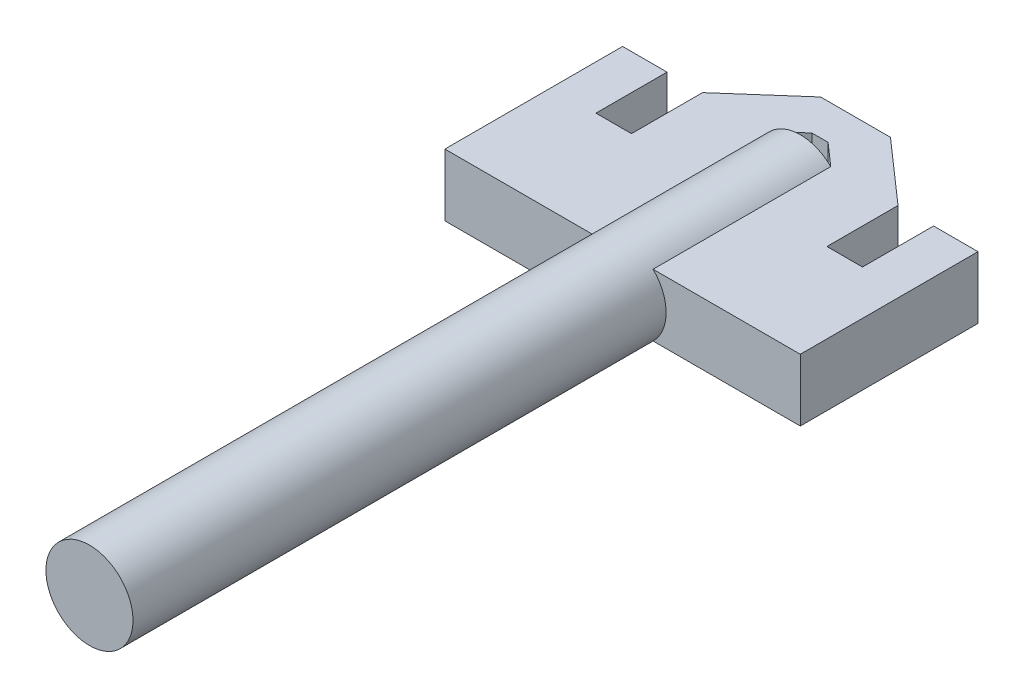
SolidWorks part; units mm, degrees
ref_plane "Front Plane" through (0, 0, 0) normal (0, 0, 1) x (1, 0, 0)
ref_plane "Top Plane" through (0, 0, 0) normal (0, 1, 0) x (1, 0, 0)
ref_plane "Right Plane" through (0, 0, 0) normal (1, 0, 0) x (0, 0, -1)
sketch "Sketch2" plane through (0, 0, 0) normal (0, 0, 1) x (1, 0, 0)
  circle A0 centre (0, 0) radius 2.45
  dimension "D1" = 4.9
extrude "Boss-Extrude1" add sketch "Sketch2" along normal blind 40
sketch "Sketch3" plane through (0, 0, 0) normal (0, 0, -1) x (-1, 0, 0)
  line L0 (-10, 1.75) -> (10, 1.75)
  line L1 (10, 1.75) -> (10, -1.75)
  line L4 (-10, 1.75) -> (-10, -1.75)
  line L5 (-10, -1.75) -> (10, -1.75)
  circle A1 centre (0, 0) radius 2.45 construction
  point P3 (10, 0)
  point P5 (0, 1.75)
  dimension "D1" = 1.75
  dimension "D4" = 20
extrude "Boss-Extrude2" add sketch "Sketch3" against normal blind 10
sketch "Sketch4" plane through (0, 0, 0) normal (0, 0, -1) x (-1, 0, 0)
  line L0 (0, 2.45) -> (0, -2.45) construction
  line L1 (-10, -1.75) -> (-1.7146, -1.75) construction
  line L2 (-7.5, 1.75) -> (-5.5, 1.75)
  line L3 (-7.5, 1.75) -> (-7.5, -1.75)
  line L4 (-7.5, -1.75) -> (-5.5, -1.75)
  line L5 (-5.5, 1.75) -> (-5.5, -1.75)
  line L6 (-7.5, 1.75) -> (-5.5, -1.75) construction
  line L7 (-7.5, -1.75) -> (-5.5, 1.75) construction
  line L8 (-1.7146, 1.75) -> (-10, 1.75) construction
  line L9 (-10, 1.75) -> (-10, -1.75) construction
  line L10 (7.5, -1.75) -> (5.5, 1.75) construction
  line L11 (7.5, 1.75) -> (5.5, -1.75) construction
  line L12 (5.5, 1.75) -> (5.5, -1.75)
  line L13 (7.5, -1.75) -> (5.5, -1.75)
  line L14 (7.5, 1.75) -> (7.5, -1.75)
  line L15 (7.5, 1.75) -> (5.5, 1.75)
  point P8 (-6.5, 0)
  point P23 (6.5, 0)
  dimension "D1" = 2.5
  dimension "D2" = 2
extrude "Cut-Extrude1" cut sketch "Sketch4" against normal blind 4
sketch "Sketch5" plane through (0, 0, 0) normal (0, 1, 0) x (1, 0, 0)
  line L0 (-1.7146, 0) -> (-0.4535, 1.1092)
  line L2 (-0.4535, 1.1092) -> (0.4535, 1.1092)
  line L3 (0.4535, 1.1092) -> (1.7146, 0)
  line L5 (-1.7146, 0) -> (-5.5, 0)
  line L6 (-5.5, 0) -> (-1.965, 3.1092)
  line L7 (-1.965, 3.1092) -> (1.965, 3.1092)
  line L8 (1.965, 3.1092) -> (5.5, 0)
  line L9 (1.7146, 0) -> (5.5, 0)
  dimension "D2" = 2
  dimension "D3" = 2.5
extrude "Boss-Extrude3" add sketch "Sketch5" along normal up to surface (1.75 mm away) and the other way up to surface (1.75 mm away) up to face at (6.1787, 1.75, 3.5) other way up to face at (6.1787, -1.75, 3.5)
